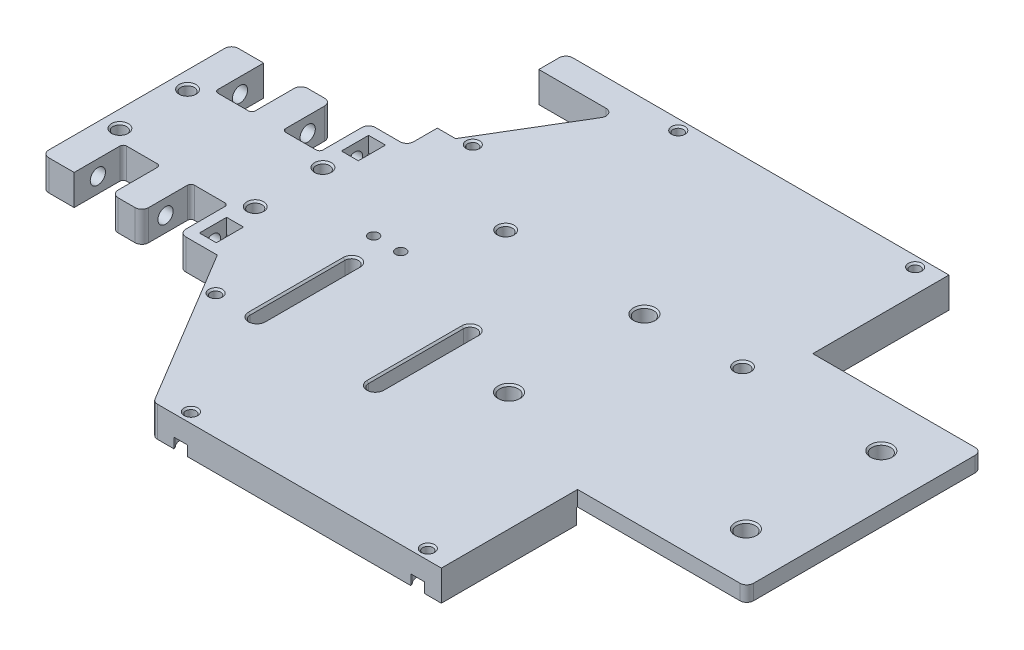
SolidWorks part; units mm, degrees
ref_plane "Front Plane" through (0, 0, 0) normal (0, 0, 1) x (1, 0, 0)
ref_plane "Top Plane" through (0, 0, 0) normal (0, 1, 0) x (1, 0, 0)
ref_plane "Right Plane" through (0, 0, 0) normal (1, 0, 0) x (0, 0, -1)
sketch "Sketch1" plane through (0, 0, 0) normal (0, 1, 0) x (1, 0, 0)
  line L0 (-78.0026, 25) -> (-28.0026, 25)
  line L1 (1.9974, 75) -> (86.9974, 75)
  line L2 (-78.0026, 25) -> (-78.0026, -25)
  line L3 (1.9974, -75) -> (86.9974, -75)
  line L4 (86.9974, 75) -> (86.9974, -75)
  line L7 (-28.0026, 25) -> (1.9974, 75)
  line L8 (1.9974, -75) -> (-28.0026, -25)
  line L9 (-28.0026, -25) -> (-78.0026, -25)
  point P0 (0, 0)
  dimension "D1" = 30
  dimension "D2" = 30
  dimension "D3" = 50
  dimension "D4" = 50
  dimension "D5" = 50
  dimension "D6" = 165
  dimension "D7" = 75
  dimension "D8" = 50
  dimension "D9" = 50
  dimension "D10" = 150
  dimension "D11" = 120.964
extrude "Boss-Extrude1" add sketch "Sketch1" along normal blind 9
sketch "Sketch3" plane through (0, 9, 0) normal (0, 1, 0) x (1, 0, 0)
  line L1 (-28.0026, 25) -> (-78.0026, 25) construction
  line L4 (-78.0026, 25) -> (-78.0026, -25) construction
  circle A0 centre (-73.0026, 10) radius 2
  circle A1 centre (-33.0026, 10) radius 2
  circle A2 centre (-33.0026, -10) radius 2
  circle A3 centre (-73.0026, -10) radius 2
  dimension "D5" = 4
  dimension "D6" = 4
  dimension "D7" = 4
  dimension "D8" = 4
  dimension "D1" = 40
  dimension "D2" = 20
  dimension "D3" = 20
  dimension "D4" = 40
  dimension "D9" = 15
  dimension "D10" = 5
  dimension "D11" = 15
  dimension "D12" = 5
extrude "Cut-Extrude1" cut sketch "Sketch3" against normal through all
sketch "Sketch4" plane through (86.9974, 0, 0) normal (1, 0, 0) x (0, 0, -1)
  line L0 (-75, 9) -> (75, 9) construction
  line L1 (-34.75, 9) -> (34.75, 9)
  line L2 (-34.75, 9) -> (-34.75, 4.5)
  line L3 (-34.75, 4.5) -> (34.75, 4.5)
  line L4 (34.75, 9) -> (34.75, 4.5)
  line L5 (-75, 9) -> (-75, 0) construction
  line L6 (75, 9) -> (75, 0) construction
  dimension "D1" = 4.5
  dimension "D2" = 40.25
  dimension "D3" = 40.25
  dimension "D4" = 69.5
extrude "Boss-Extrude2" add sketch "Sketch4" along normal blind 50
sketch "Sketch5" plane through (86.9974, 0, 0) normal (1, 0, 0) x (0, 0, -1)
  line L0 (-75, 0) -> (75, 0) construction
  line L1 (-35, 4.5) -> (35, 4.5)
  line L2 (-35, 4.5) -> (-35, 0)
  line L3 (-35, 0) -> (35, 0)
  line L4 (35, 4.5) -> (35, 0)
  line L6 (34.75, 4.5) -> (34.75, 9) construction
  dimension "D1" = 70
  dimension "D2" = 0.25
extrude "Cut-Extrude2" cut sketch "Sketch5" against normal blind 45
sketch "Sketch6" plane through (0, 9, 0) normal (0, 1, 0) x (1, 0, 0)
  line L2 (136.9974, 34.75) -> (136.9974, -34.75) construction
  circle A0 centre (51.9974, 20) radius 2.75
  circle A1 centre (51.9974, -20) radius 2.75
  circle A2 centre (121.9974, 20) radius 2.75
  circle A3 centre (121.9974, -20) radius 2.75
  dimension "D1" = 5.5
  dimension "D2" = 5.5
  dimension "D3" = 5.5
  dimension "D4" = 5.5
  dimension "D5" = 40
  dimension "D6" = 40
  dimension "D7" = 20
  dimension "D8" = 70
  dimension "D9" = 0
  dimension "D10" = 70
  dimension "D11" = 15
  dimension "D12" = 15
extrude "Cut-Extrude4" cut sketch "Sketch6" against normal blind 50
fillet "Fillet1" radius 2 4 edges at (-28.0026, 4.5, -25) (1.9974, 4.5, -75) (1.9974, 4.5, 75) (-28.0026, 4.5, 25)
chamfer "Chamfer1" distance 0.5 angle 45 4 edges at (51.9974, 9, 22.75) (121.9974, 9, 22.75) (121.9974, 9, -17.25) (51.9974, 9, -17.25)
fillet "Fillet2" radius 2 2 edges at (136.9974, 6.75, -34.75) (136.9974, 6.75, 34.75)
sketch "Sketch7" plane through (0, 9, 0) normal (0, 1, 0) x (1, 0, 0)
  line L0 (-78.0026, -25) -> (-29.1349, -25) construction
  line L1 (-68.5026, -25) -> (-57.5026, -25)
  line L2 (-68.5026, -25) -> (-68.5026, -13.5)
  line L3 (-68.5026, -13.5) -> (-57.5026, -13.5)
  line L4 (-57.5026, -25) -> (-57.5026, -13.5)
  line L5 (-78.0026, 25) -> (-78.0026, -25) construction
  line L6 (-48.5026, -25) -> (-37.5026, -25)
  line L7 (-48.5026, -25) -> (-48.5026, -13.5)
  line L8 (-48.5026, -13.5) -> (-37.5026, -13.5)
  line L9 (-37.5026, -25) -> (-37.5026, -13.5)
  dimension "D1" = 9.5
  dimension "D2" = 11
  dimension "D3" = 9
  dimension "D4" = 11
  dimension "D5" = 11.5
  dimension "D6" = 11.5
extrude "Cut-Extrude5" cut sketch "Sketch7" against normal through all
sketch "Sketch8" plane through (-78.0026, 0, 0) normal (-1, 0, 0) x (0, 0, 1)
  line L0 (-25, 9) -> (25, 9) construction
  line L1 (25, 9) -> (25, 0) construction
  circle A0 centre (21, 4.5) radius 2.25
  dimension "D2" = 4.5
  dimension "D1" = 4.5
  dimension "D3" = 4
extrude "Cut-Extrude6" cut sketch "Sketch8" against normal blind 50
sketch "Sketch10" plane through (-78.0026, 0, 0) normal (-1, 0, 0) x (0, 0, 1)
  circle A0 centre (21, 4.5) radius 3.5
  dimension "D1" = 7
extrude "Cut-Extrude8" cut sketch "Sketch10" against normal blind 4
sketch "Sketch11" plane through (-37.5026, 0, 0) normal (-1, 0, 0) x (0, 0, 1)
  line L33 (16.9585, 4.5) -> (16.9585, 11.7743)
  line L37 (16.9585, 4.5) -> (18.9793, 1)
  line L38 (18.9793, 1) -> (23.0207, 1)
  line L39 (23.0207, 1) -> (25.0415, 4.5)
  line L40 (16.9585, 11.7743) -> (25.0415, 11.7743)
  line L41 (25.0415, 11.7743) -> (25.0415, 4.5)
  line L43 (23.0207, 8) -> (18.9793, 8) [skipped]
  line L44 (25.0415, 4.5) -> (24.0311, 6.25) [skipped]
  line L45 (15.4689, 1.9199) -> (14.4585, 0.1699) [skipped]
  arc A1 (17.9689, 2.75) -> (24.0311, 2.75) centre (21, 4.5) ccw construction
extrude "Cut-Extrude9" cut sketch "Sketch11" against normal blind 5 from offset 3 offset against normal yes
fillet "Fillet4" radius 1 4 edges at (-48.5026, 4.5, 13.5) (-37.5026, 4.5, 13.5) (-57.5026, 4.5, 13.5) (-68.5026, 4.5, 13.5)
mirror "Mirror2" about plane through (0, 0, 0) normal (0, 0, 1) of "Fillet4", "Cut-Extrude9", "Cut-Extrude8", "Cut-Extrude6", "Cut-Extrude5"
sketch "Sketch12" plane through (0, 9, 0) normal (0, 1, 0) x (1, 0, 0)
  line L0 (-6.5026, -10) -> (-6.5026, -38)
  line L1 (-2.5026, -10) -> (-2.5026, -38)
  line L2 (3.1298, -75) -> (86.9974, -75) construction
  line L3 (86.9974, -75) -> (86.9974, -34.75) construction
  line L4 (28.4974, -10) -> (28.4974, -38)
  line L5 (32.4974, -10) -> (32.4974, -38)
  arc A0 (-2.5026, -10) -> (-6.5026, -10) centre (-4.5026, -10) ccw
  arc A2 (-6.5026, -38) -> (-2.5026, -38) centre (-4.5026, -38) ccw
  arc A3 (32.4974, -10) -> (28.4974, -10) centre (30.4974, -10) ccw
  arc A4 (28.4974, -38) -> (32.4974, -38) centre (30.4974, -38) ccw
  dimension "D2" = 4
  dimension "D5" = 4
  dimension "D6" = 4
  dimension "D7" = 4
  dimension "D12" = 28
  dimension "D3" = 37
  dimension "D4" = 91.5
  dimension "D9" = 35
  dimension "D8" = 28
extrude "Cut-Extrude10" cut sketch "Sketch12" against normal blind 10
sketch "Sketch15" plane through (0, 9, 0) normal (0, 1, 0) x (1, 0, 0)
  line L0 (86.9974, 75) -> (3.1298, 75) construction
  line L2 (1.4148, 74.029) -> (-27.42, 25.971) construction
  line L3 (-4.95, 0) -> (4.95, 0) construction
  line L4 (86.9974, 34.75) -> (86.9974, 75) construction
  circle A0 centre (79.9974, 72) radius 1.5
  circle A1 centre (9.9974, 72) radius 1.5
  circle A2 centre (-16.704, 38) radius 1.5
  circle A7 centre (-16.704, -38) radius 1.5
  circle A8 centre (9.9974, -72) radius 1.5
  circle A9 centre (79.9974, -72) radius 1.5
  dimension "D1" = 3
  dimension "D2" = 3
  dimension "D3" = 3
  dimension "D4" = 37
  dimension "D5" = 70
  dimension "D6" = 3
  dimension "D7" = 3
  dimension "D8" = 3
  dimension "D9" = 7
extrude "Cut-Extrude12" cut sketch "Sketch15" against normal blind 10
sketch "Sketch17" plane through (0, 0, 0) normal (0, -1, 0) x (1, 0, 0)
  line L0 (4.95, 0) -> (-4.95, 0) construction
  circle A0 centre (9.9974, 72) radius 3.25
  circle A1 centre (-16.704, 38) radius 3.25
  circle A2 centre (79.9974, 72) radius 3.25
  circle A3 centre (79.9974, -72) radius 3.25
  circle A4 centre (-16.704, -38) radius 3.25
  circle A5 centre (9.9974, -72) radius 3.25
  dimension "D1" = 6.5
  dimension "D2" = 6.5
  dimension "D3" = 6.5
extrude "Cut-Extrude14" cut sketch "Sketch17" against normal blind 3
chamfer "Chamfer2" distance 1 angle 45 10 edges at (-19.9196, 1.5, 38.4716) (-18.6333, 1.5, 40.6154) (81.2474, 1.5, 75) (78.7474, 1.5, 75) (8.7474, 1.5, 75) (11.2474, 1.5, 75) (81.2474, 1.5, -75) (78.7474, 1.5, -75) (11.2474, 1.5, -75) (8.7474, 1.5, -75) first distance on face at (-16.5968, 1.5, 37.9357) first distance on face at (79.9974, 1.5, 71.875) first distance on face at (9.9974, 1.5, 71.875) first distance on face at (79.9974, 1.5, -71.875) first distance on face at (9.9974, 1.5, -71.875)
sketch "Sketch18" plane through (0, 0, 25) normal (0, 0, 1) x (1, 0, 0)
  line L1 (-37.5026, 9) -> (-25.5026, 9)
  line L2 (-37.5026, 9) -> (-37.5026, 0)
  line L3 (-37.5026, 0) -> (-25.5026, 0)
  line L4 (-25.5026, 9) -> (-25.5026, 0)
  dimension "D1" = 12
extrude "Boss-Extrude3" add sketch "Sketch18" along normal blind 3
mirror "Mirror3" about plane through (0, 0, 0) normal (0, 0, 1) of "Boss-Extrude3"
sketch "Sketch20" plane through (0, 9, 0) normal (0, 1, 0) x (1, 0, 0)
  line L0 (86.9974, 34.75) -> (86.9974, 75) construction
  line L2 (86.9974, 75) -> (3.1298, 75) construction
  circle A0 centre (9.9974, 21) radius 2
  circle A1 centre (79.9974, 21) radius 2
  dimension "D3" = 4
  dimension "D4" = 4
  dimension "D2" = 54
  dimension "D5" = 70
  dimension "D6" = 7
  dimension "D7" = 54
extrude "Cut-Extrude15" cut sketch "Sketch20" against normal through all
sketch "Sketch23" plane through (0, 0, 0) normal (1, 0, 0) x (0, 0, -1)
  line L0 (74.029, 0) -> (40.6154, 0) construction
  line L1 (75, 9) -> (67, 9)
  line L2 (75, 9) -> (75, 0)
  line L3 (75, 0) -> (67, 0)
  line L4 (67, 9) -> (67, 0)
  line L5 (74.029, 9) -> (28, 9) construction
  line L6 (28, 0) -> (37, 0)
  line L7 (28, 0) -> (28, 9)
  line L8 (28, 9) -> (37, 9)
  line L9 (37, 0) -> (37, 9)
  dimension "D1" = 8
  dimension "D2" = 9
extrude "Boss-Extrude5" add sketch "Sketch23" against normal up to vertex (26.2026 mm away) and the other way blind 3 up to point (-26.2026, 9, -28)
fillet "Fillet5" radius 2 1 edges at (-26.2026, 4.5, -28)
sketch "Sketch24" plane through (0, 0, 0) normal (0, -1, 0) x (1, 0, 0)
  circle A1 centre (9.9974, -72) radius 3.25
  circle A2 centre (-16.704, -38) radius 3.25
extrude "Cut-Extrude17" cut sketch "Sketch24" against normal up to surface (3 mm away) up to face at (9.9974, 3, -70.5)
sketch "Sketch25" plane through (0, 3, 0) normal (0, -1, 0) x (1, 0, 0)
  circle A1 centre (-16.704, -38) radius 1.5
extrude "Cut-Extrude18" cut sketch "Sketch25" against normal through all
sketch "Sketch26" plane through (-26.2026, 0, 0) normal (-1, 0, 0) x (0, 0, 1)
  line L0 (-75, 0) -> (-75, 9) construction
  line L1 (-75, 9) -> (-67, 9) construction
  circle A0 centre (-70, 4.5) radius 1.25
  circle A1 centre (-33, 4.5) radius 1.25
  dimension "D1" = 2.5
  dimension "D2" = 2.5
  dimension "D3" = 37
  dimension "D4" = 5
  dimension "D5" = 4.5
extrude "Cut-Extrude20" cut sketch "Sketch26" against normal blind 5
chamfer "Chamfer3" distance 1 angle 45 2 edges at (-18.6333, 1.5, -40.6154) (-19.9196, 1.5, -38.4716) first distance on face at (-16.5968, 1.5, -37.9357)
fillet "Fillet6" radius 2 2 edges at (-2.8026, 4.5, -67) (-26.2026, 4.5, -75)
chamfer "Chamfer4" distance 0.5 angle 45 20 edges at (79.9974, 9, 70.5) (79.9974, 9, -19) (79.9974, 9, -70.5) (9.9974, 9, -70.5) (-16.704, 9, -36.5) (-73.0026, 9, 12) (-73.0026, 9, -8) (-33.0026, 9, -8) (-33.0026, 9, 12) (-16.704, 9, 36.5) (9.9974, 9, 70.5) (-4.5026, 9, 40) (-4.5026, 9, 8) (9.9974, 9, -19) (30.4974, 9, 40) (30.4974, 9, 8) (32.4974, 9, 24) (28.4974, 9, 24) (-2.5026, 9, 24) (-6.5026, 9, 24)
sketch "Sketch27" plane through (0, 0, 0) normal (0, -1, 0) x (1, 0, 0)
  circle A0 centre (9.9974, -21) radius 3.5
  dimension "D1" = 7
extrude "Cut-Extrude21" cut sketch "Sketch27" against normal blind 3
sketch "Sketch28" plane through (0, 9, 0) normal (0, 1, 0) x (1, 0, 0)
  line L0 (-48.5026, 25) -> (-57.5026, 25) construction
  line L1 (-78.0026, 25) -> (-78.0026, -25) construction
  circle A0 centre (-8.0026, 0) radius 1.5
  circle A1 centre (-0.0026, 0) radius 1.5
  dimension "D3" = 3
  dimension "D4" = 3
  dimension "D1" = 25
  dimension "D2" = 25
  dimension "D5" = 70
  dimension "D6" = 8
extrude "Cut-Extrude22" cut sketch "Sketch28" against normal blind 10
sketch "Sketch29" plane through (0, 0, 0) normal (0, -1, 0) x (1, 0, 0)
  circle A0 centre (-8.0026, 0) radius 2.75
  circle A1 centre (-0.0026, 0) radius 2.75
  dimension "D1" = 5.5
  dimension "D2" = 5.5
extrude "Cut-Extrude23" cut sketch "Sketch29" against normal blind 3
sketch "Sketch30" plane through (0, 0, -25) normal (0, 0, -1) x (-1, 0, 0)
  line L1 (57.5026, 9) -> (48.5026, 9)
  line L2 (57.5026, 9) -> (57.5026, 0)
  line L3 (57.5026, 0) -> (48.5026, 0)
  line L4 (48.5026, 9) -> (48.5026, 0)
  line L5 (68.5026, 9) -> (78.0026, 9)
  line L6 (68.5026, 9) -> (68.5026, 0)
  line L7 (68.5026, 0) -> (78.0026, 0)
  line L8 (78.0026, 9) -> (78.0026, 0)
extrude "Boss-Extrude6" add sketch "Sketch30" along normal blind 3
mirror "Mirror4" about plane through (0, 0, 0) normal (0, 0, 1) of "Boss-Extrude6"
fillet "Fillet7" radius 2 8 edges at (-37.5026, 4.5, 28) (-37.5026, 4.5, -28) (-57.5026, 4.5, -28) (-48.5026, 4.5, -28) (-48.5026, 4.5, 28) (-57.5026, 4.5, 28) (-78.0026, 4.5, 28) (-78.0026, 4.5, -28)
equation "\"D5@Sketch12\"=\"D2@Sketch12\""
